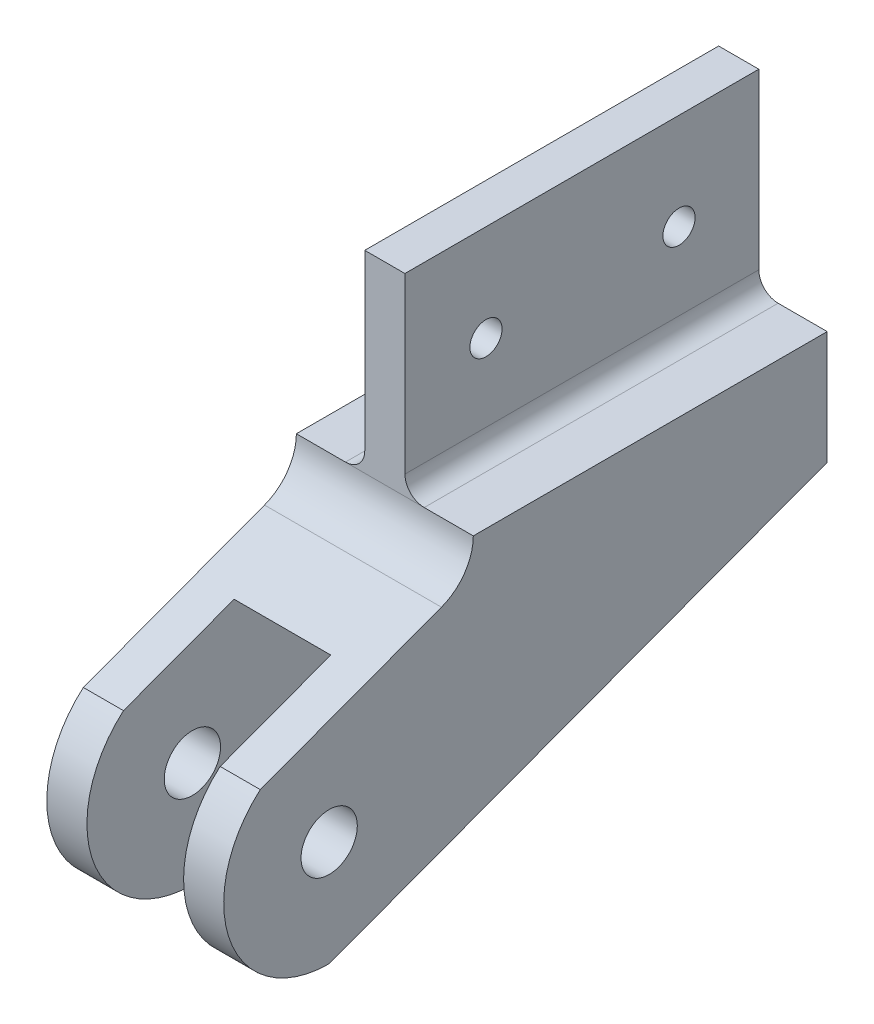
SolidWorks part; units mm, degrees
ref_plane "Front Plane" through (0, 0, 0) normal (0, 0, 1) x (1, 0, 0)
ref_plane "Top Plane" through (0, 0, 0) normal (0, 1, 0) x (1, 0, 0)
ref_plane "Right Plane" through (0, 0, 0) normal (1, 0, 0) x (0, 0, -1)
sketch "Sketch1" plane through (0, 0, 0) normal (1, 0, 0) x (0, 0, -1)
  line L0 (0, 0) -> (69.85, 0)
  line L1 (69.85, 0) -> (69.85, -60.452)
  line L2 (-6.2874, -47.1466) -> (-28.448, -55.3886)
  line L3 (0, 0) -> (0, -38.1)
  line L4 (69.85, -60.452) -> (-28.448, -97.0114)
  line L5 (0, -38.1) -> (69.85, -38.1)
  line L6 (0, -19.05) -> (69.85, -19.05) construction
  line L7 (-28.448, -76.2) -> (-28.448, -55.3886) construction
  line L8 (-28.448, -97.0114) -> (-28.448, -76.2) construction
  line L9 (-28.448, -55.3886) -> (-42.0473, -60.4465)
  line L10 (-20.2081, -52.324) -> (69.85, -52.324)
  circle A0 centre (-28.448, -76.2) radius 5.5562
  arc A1 (0, -38.1) -> (-6.2874, -47.1466) centre (-9.652, -38.1) cw
  circle A2 centre (16.002, -19.05) radius 3.175
  circle A3 centre (54.102, -19.05) radius 3.175
  arc A4 (-42.0473, -60.4465) -> (-28.448, -97.0114) centre (-28.448, -76.2) ccw
  dimension "D3" = 9.652
  dimension "D5" = 6.35
  dimension "D11" = 11.1125
  dimension "D1" = 69.85
  dimension "D2" = 60.452
  dimension "D4" = 22.352
  dimension "D6" = 19.05
  dimension "D7" = 15.748
  dimension "D8" = 38.1
  dimension "D9" = 38.1
  dimension "D10" = 44.45
  dimension "D12" = 14.224
extrude "Boss-Extrude1" add sketch "Sketch1" along normal mid plane 7.9248 contours L3 L5 L1 L0 A3 A2 | L5 A1 L2 L10 L1 region at (0, -19.05, -34.9219) region at (0, -45.5265, -31.7145)
extrude "Boss-Extrude2" add sketch "Sketch1<3>" along normal mid plane 34.925 contours L5 A1 L2 L10 L1 region at (0, -45.5265, -31.7145)
sketch "Sketch1<3>" plane through (0, 0, 0) normal (1, 0, 0) x (0, 0, -1) same geometry as "Sketch1"
extrude "Boss-Extrude4" add sketch "Sketch1<5>" against normal blind 7.9248 from vertex contours L9 A4 L4 L1 L10 L2 A0 region at (0, -69.319, -0.7828) starting at point (17.4625, -52.324, 20.2081)
sketch "Sketch1<5>" plane through (0, 0, 0) normal (1, 0, 0) x (0, 0, -1) same geometry as "Sketch1"
extrude "Boss-Extrude5" add sketch "Sketch1<6>" along normal blind 7.9248 from vertex contours L9 A4 L4 L1 L10 L2 A0 region at (0, -69.319, -0.7828) starting at point (-17.4625, -52.324, 20.2081)
sketch "Sketch1<6>" plane through (0, 0, 0) normal (1, 0, 0) x (0, 0, -1) same geometry as "Sketch1"
fillet "Fillet1" radius 3.81 2 edges at (-3.9624, -38.1, -34.925) (3.9624, -38.1, -34.925)
